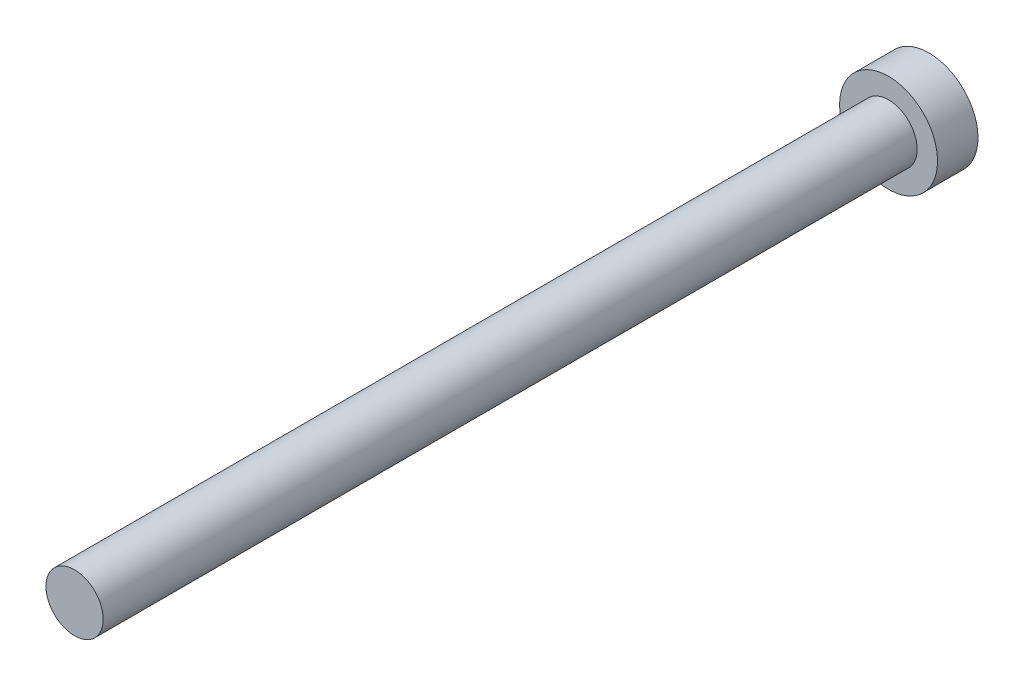
SolidWorks part; units mm, degrees
ref_plane "Front Plane" through (0, 0, 0) normal (0, 0, 1) x (1, 0, 0)
ref_plane "Top Plane" through (0, 0, 0) normal (0, 1, 0) x (1, 0, 0)
ref_plane "Right Plane" through (0, 0, 0) normal (1, 0, 0) x (0, 0, -1)
sketch "Sketch1" plane through (0, 0, 0) normal (0, 0, 1) x (1, 0, 0)
  circle A0 centre (0, 0) radius 1.5
  dimension "D1" = 3
extrude "Boss-Extrude1" add sketch "Sketch1" along normal blind 42
sketch "Sketch2" plane through (0, 0, 0) normal (0, 0, -1) x (-1, 0, 0)
  circle A0 centre (0, 0) radius 2.75
  dimension "D1" = 5.5
extrude "Boss-Extrude2" add sketch "Sketch2" against normal blind 2.2
scale "Escala1" scale about origin uniform scaling yes scale factor 1.5
scale "Escala2" scale about origin uniform scaling yes scale factor 1.5
sketch "Croquis1" plane through (0, 0, 94.5) normal (0, 0, 1) x (1, 0, 0)
  circle A2 centre (0, 0) radius 3.375 construction
  circle A3 centre (0, 0) radius 3.375 construction
  circle A4 centre (0, 0) radius 3.5
  dimension "D1" = 7
extrude "Saliente-Extruir1" add sketch "Croquis1" along normal blind 10 and the other way up to next
sketch "Croquis2" plane through (0, 0, 0) normal (0, 0, -1) x (-1, 0, 0)
  circle A0 centre (0, 0) radius 5.99
  dimension "D1" = 11.98
extrude "Cortar-Extruir1" cut sketch "Croquis2" against normal through all both and the other way through all flip side to cut
